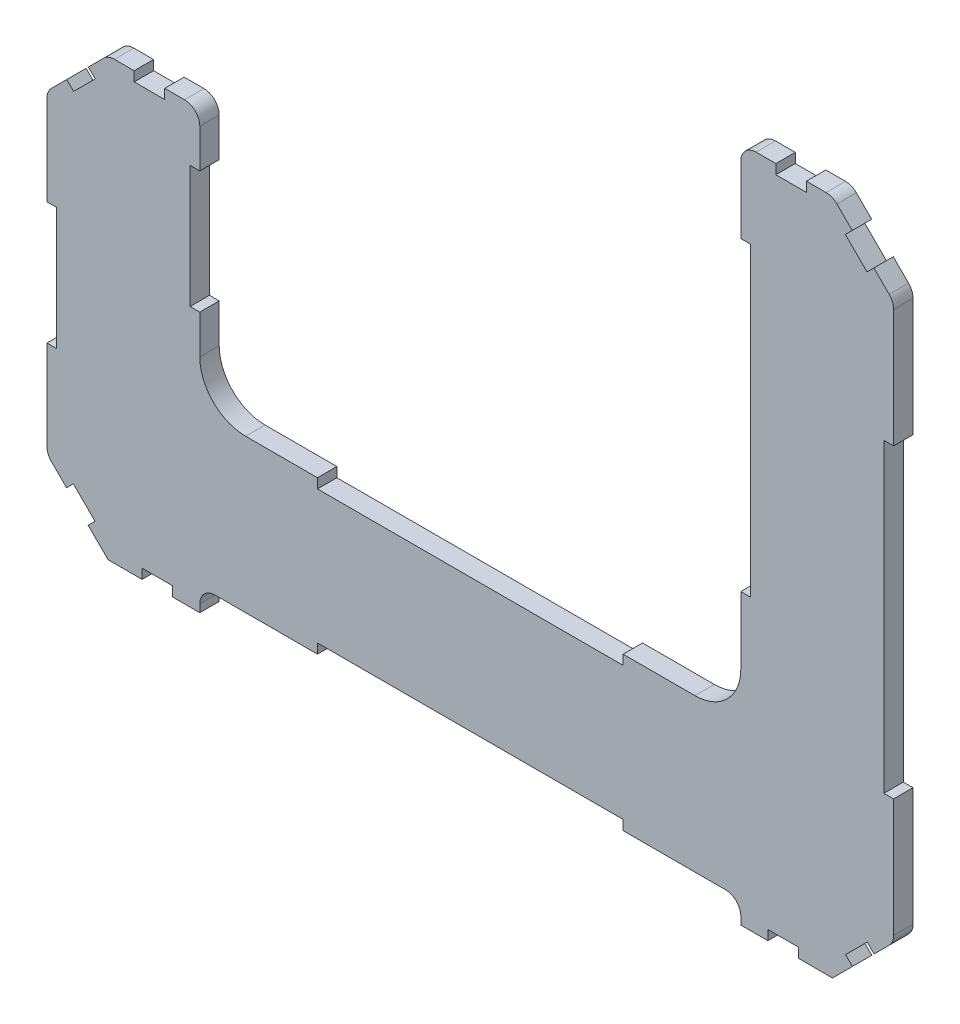
SolidWorks part; units mm, degrees
material "Cedar"
ref_plane "Front Plane" through (0, 0, 0) normal (0, 0, 1) x (1, 0, 0)
ref_plane "Top Plane" through (0, 0, 0) normal (0, 1, 0) x (1, 0, 0)
ref_plane "Right Plane" through (0, 0, 0) normal (1, 0, 0) x (0, 0, -1)
sketch "Sketch2" plane through (0, 0, 0) normal (0, 0, 1) x (1, 0, 0)
  line L0 (-138.5, 85.3385) -> (-88.5, 85.3385)
  line L1 (-88.5, 85.3385) -> (-88.5, 0)
  line L2 (-88.5, 0) -> (88.5, 0)
  line L3 (88.5, 0) -> (88.5, 164)
  line L4 (88.5, 164) -> (138.5, 164)
  line L5 (138.5, 164) -> (138.5, -57.5)
  line L6 (138.5, -57.5) -> (88.5, -57.5)
  line L7 (88.5, -57.5) -> (88.5, -50)
  line L8 (88.5, -50) -> (-88.5, -50)
  line L9 (-88.5, -50) -> (-88.5, -57.5)
  line L10 (-88.5, -57.5) -> (-138.5, -57.5)
  line L11 (-138.5, -57.5) -> (-138.5, 85.3385)
  line L12 (-33.5, 0) -> (-33.5, 124) construction
  point P10 (-33.5, 0)
  point P14 (88.5, 124)
  point P15 (-33.5, 85.3385)
  dimension "D1" = 124
  dimension "D2" = 122
  dimension "D3" = 55
  dimension "D4" = 40
  dimension "D5" = 50
  dimension "D6" = 50
  dimension "D7" = 7.5
extrude "Boss-Extrude1" add sketch "Sketch2" along normal blind 3.175 and the other way blind 3.175
chamfer "Chamfer1" distance 20 angle 45 4 edges at (-138.5, -57.5, 0) (138.5, -57.5, 0) (138.5, 164, 0) (-138.5, 85.3385, 0)
fillet "Fillet1" radius 15 2 edges at (88.5, 0, 0) (-88.5, 0, 0)
fillet "Fillet2" radius 5 10 edges at (138.5, -37.5, 0) (88.5, -50, 0) (-88.5, -50, 0) (-138.5, -37.5, 0) (-138.5, 65.3385, 0) (-118.5, 85.3385, 0) (-88.5, 85.3385, 0) (138.5, 144, 0) (118.5, 164, 0) (88.5, 164, 0)
sketch "Sketch3" plane through (0, 0, 3.175) normal (0, 0, 1) x (1, 0, 0)
  line L0 (-94.6381, 69.9757) -> (-94.6381, 14.7992)
  line L1 (-94.6381, 14.7992) -> (-97.8131, 14.7992)
  line L2 (-97.8131, 14.7992) -> (-97.8131, 69.9757)
  line L3 (-97.8131, 69.9757) -> (-94.6381, 69.9757)
  line L4 (-127.4635, 65.4691) -> (-114.3536, 78.579)
  line L5 (-114.3536, 78.579) -> (-112.1085, 76.3339)
  line L6 (-112.1085, 76.3339) -> (-125.2184, 63.2241)
  line L7 (-125.2184, 63.2241) -> (-127.4635, 65.4691)
  line L8 (-129.3392, 54.7846) -> (-126.1642, 54.7846)
  line L9 (-126.1642, 54.7846) -> (-126.1642, -28.3138)
  line L10 (-126.1642, -28.3138) -> (-129.3392, -28.3138)
  line L11 (-129.3392, -28.3138) -> (-129.3392, 54.7846)
  line L12 (-127.4635, -37.1329) -> (-125.2184, -34.8879)
  line L13 (-125.2184, -34.8879) -> (-110.9382, -49.1681)
  line L14 (-110.9382, -49.1681) -> (-113.1832, -51.4132)
  line L15 (-113.1832, -51.4132) -> (-127.4635, -37.1329)
  line L16 (-67.7784, -44.3183) -> (-67.7784, -41.1433)
  line L17 (-67.7784, -41.1433) -> (53.0181, -41.1433)
  line L18 (53.0181, -41.1433) -> (53.0181, -44.3183)
  line L19 (53.0181, -44.3183) -> (-67.7784, -44.3183)
  line L20 (114.9313, -49.5303) -> (117.1763, -51.7753)
  line L21 (117.1763, -51.7753) -> (131.7883, -37.1634)
  line L22 (131.7883, -37.1634) -> (129.5432, -34.9183)
  line L23 (129.5432, -34.9183) -> (114.9313, -49.5303)
  line L24 (-67.7784, -4.1746) -> (-67.7784, -7.3496)
  line L25 (-67.7784, -7.3496) -> (63.5847, -7.3496)
  line L26 (63.5847, -7.3496) -> (63.5847, -4.1746)
  line L27 (63.5847, -4.1746) -> (-67.7784, -4.1746)
  line L28 (92.7516, 20.9162) -> (91.2159, 151.9937)
  line L29 (91.2159, 151.9937) -> (94.3909, 151.9937)
  line L30 (94.3909, 151.9937) -> (95.9266, 20.9162)
  line L31 (95.9266, 20.9162) -> (92.7516, 20.9162)
  line L32 (96.8341, 161.8762) -> (96.8341, 158.7012)
  line L33 (96.8341, 158.7012) -> (112.5649, 158.7012)
  line L34 (112.5649, 158.7012) -> (112.5649, 161.8762)
  line L35 (112.5649, 161.8762) -> (96.8341, 161.8762)
  line L37 (117.7781, 156.4535) -> (120.0231, 158.6985)
  line L38 (120.0231, 158.6985) -> (133.8694, 144.8523)
  line L39 (133.8694, 144.8523) -> (131.6243, 142.6072)
  line L40 (131.6243, 142.6072) -> (117.7781, 156.4535)
  line L41 (129.9213, 134.1701) -> (133.0963, 134.1701)
  line L42 (133.0963, 134.1701) -> (133.0963, -24.961)
  line L43 (133.0963, -24.961) -> (129.9213, -24.961)
  line L44 (129.9213, -24.961) -> (129.9213, 134.1701)
  line L45 (118.5, -57.5) -> (137.0355, -38.9645) construction
  line L46 (-137.0355, -38.9645) -> (-118.5, -57.5) construction
  line L47 (-119.9645, 83.874) -> (-137.0355, 66.8029) construction
  line L48 (137.0355, 145.4645) -> (119.9645, 162.5355) construction
  dimension "D1" = 3.175
extrude "Cut-Extrude1" [suppressed] cut sketch "Sketch3" against normal through all
sketch "magnets" plane through (0, 0, 3.175) normal (0, 0, 1) x (1, 0, 0)
  point P0 (94.6751, 158.4052)
  point P1 (114.7572, -50)
  point P2 (131.9288, 140.6094)
  point P3 (131.9288, -32.8111)
  point P4 (0, -44.1618)
  point P5 (-114.0039, -50)
  point P6 (-130.8821, -32.8111)
  point P9 (-130.8821, 62.3605)
  point P10 (-93.5499, 79.7316)
  point P12 (0, -4.7392)
sketch "Sketch4" plane through (0, 0, 3.175) normal (0, 0, 1) x (1, 0, 0)
  line L0 (99.9645, 164) -> (99.9645, 160.825)
  line L1 (116.4289, 164) -> (93.5, 164) construction
  line L2 (99.9645, 160.825) -> (109.9645, 160.825)
  line L3 (109.9645, 160.825) -> (109.9645, 164)
  line L4 (124.9645, 157.5355) -> (122.7194, 155.2905)
  line L5 (137.0355, 145.4645) -> (119.9645, 162.5355) construction
  line L6 (122.7194, 155.2905) -> (129.7905, 148.2194)
  line L7 (129.7905, 148.2194) -> (132.0355, 150.4645)
  line L8 (88.5, 137) -> (91.675, 137)
  line L9 (88.5, 159) -> (88.5, 15) construction
  line L10 (91.675, 137) -> (91.675, 37)
  line L11 (91.675, 37) -> (88.5, 37)
  line L12 (138.5, 103.25) -> (135.325, 103.25)
  line L13 (138.5, -35.4289) -> (138.5, 141.9289) construction
  line L14 (135.325, 103.25) -> (135.325, 3.25)
  line L15 (135.325, 3.25) -> (138.5, 3.25)
  line L16 (-50, 0) -> (-50, -3.175)
  line L17 (73.5, 0) -> (-73.5, 0) construction
  line L18 (-50, -3.175) -> (50, -3.175)
  line L19 (50, -3.175) -> (50, 0)
  line L20 (-50, -50) -> (-50, -46.825)
  line L21 (-83.5, -50) -> (83.5, -50) construction
  line L22 (-50, -46.825) -> (50, -46.825)
  line L23 (50, -46.825) -> (50, -50)
  line L24 (-135.325, -6.0808) -> (-138.5, -6.0808)
  line L25 (-138.5, 63.2674) -> (-138.5, -35.4289) construction
  line L26 (-135.325, 33.9192) -> (-135.325, -6.0808)
  line L27 (-135.325, 33.9192) -> (-138.5, 33.9192)
  line L28 (-132.0355, 71.8029) -> (-129.7905, 69.5579)
  line L29 (-119.9645, 83.874) -> (-137.0355, 66.8029) construction
  line L30 (-129.7905, 69.5579) -> (-122.7194, 76.6289)
  line L31 (-122.7194, 76.6289) -> (-124.9645, 78.874)
  line L32 (-109.9645, 85.3385) -> (-109.9645, 82.1635)
  line L33 (-93.5, 85.3385) -> (-116.4289, 85.3385) construction
  line L35 (-109.9645, 82.1635) -> (-99.9645, 82.1635)
  line L36 (-88.5, 67.6692) -> (-91.675, 67.6692)
  line L37 (-88.5, 15) -> (-88.5, 80.3385) construction
  line L38 (-91.675, 67.6692) -> (-91.675, 27.6692)
  line L39 (-91.675, 27.6692) -> (-88.5, 27.6692)
  line L40 (-107.375, -57.5) -> (-107.375, -54.325)
  line L41 (-118.5, -57.5) -> (-88.5, -57.5) construction
  line L42 (-107.375, -54.325) -> (-97.375, -54.325)
  line L43 (-97.375, -54.325) -> (-97.375, -57.5)
  line L44 (97.375, -57.5) -> (97.375, -54.325)
  line L45 (88.5, -57.5) -> (118.5, -57.5) construction
  line L46 (97.375, -54.325) -> (107.375, -54.325)
  line L47 (107.375, -54.325) -> (107.375, -57.5)
  line L48 (-132.0988, -43.9012) -> (-129.8537, -41.6561)
  line L49 (-137.0355, -38.9645) -> (-118.5, -57.5) construction
  line L50 (-129.8537, -41.6561) -> (-122.7827, -48.7272)
  line L51 (-122.7827, -48.7272) -> (-125.0277, -50.9723)
  line L52 (125.0277, -50.9723) -> (122.7827, -48.7272)
  line L53 (118.5, -57.5) -> (137.0355, -38.9645) construction
  line L54 (122.7827, -48.7272) -> (129.8537, -41.6561)
  line L55 (129.8537, -41.6561) -> (132.0988, -43.9012)
  line L56 (-128.5633, -47.4367) -> (-126.3182, -45.1917) construction
  line L57 (-102.375, -57.5) -> (-102.375, -54.325)
  line L58 (102.375, -57.5) -> (102.375, -54.325)
  line L59 (-128.5, 75.3385) -> (-126.2549, 73.0934) construction
  line L60 (-104.9645, 82.1635) -> (-104.9645, 85.3385) construction
  line L61 (126.2549, 151.7549) -> (128.5, 154) construction
  line L62 (126.3182, -45.1917) -> (128.5633, -47.4367) construction
  line L63 (88.5, -57.5) -> (116.25, -57.5) construction
  line L64 (120.091, -55.909) -> (137.0355, -38.9645) construction
  line L65 (120.091, -55.909) -> (118.5, -57.5) construction
  line L66 (118.5, -57.5) -> (116.25, -57.5) construction
  line L67 (-88.5, -57.5) -> (-116.25, -57.5) construction
  line L68 (-116.25, -57.5) -> (-118.5, -57.5) construction
  line L69 (-118.5, -57.5) -> (-120.091, -55.909) construction
  line L70 (-120.091, -55.909) -> (-137.0355, -38.9645) construction
  line L71 (-99.9645, 82.1635) -> (-99.9645, 85.3385)
  point P95 (0, -46.825)
  point P97 (0, -50)
  point P99 (0, -3.175)
  point P101 (135.325, 53.25)
  point P103 (138.5, 53.25)
  point P104 (91.675, 87)
  point P105 (88.5, 87)
  point P106 (104.9645, 160.825)
  point P107 (104.9645, 164)
  point P108 (128.5, 154)
  point P109 (126.2549, 151.7549)
  point P112 (-135.325, 13.9192)
  point P113 (-138.5, 13.9192)
  point P114 (-91.675, 47.6692)
  point P115 (-88.5, 47.6692)
  point P116 (126.3182, -45.1917)
  point P117 (127.7678, -48.2322)
  line M1 (118.5, -57.5) -> (137.0355, -38.9645)
  line M3 (138.5, -35.4289) -> (138.5, 141.9289)
  line M5 (137.0355, 145.4645) -> (119.9645, 162.5355)
  line M7 (116.4289, 164) -> (93.5, 164)
  line M9 (88.5, 159) -> (88.5, 15)
  line M11 (73.5, 0) -> (-73.5, 0)
  line M13 (-88.5, 15) -> (-88.5, 80.3385)
  line M15 (-93.5, 85.3385) -> (-116.4289, 85.3385)
  line M17 (-119.9645, 83.874) -> (-137.0355, 66.8029)
  line M19 (-138.5, 63.2674) -> (-138.5, -35.4289)
  line M21 (-137.0355, -38.9645) -> (-118.5, -57.5)
  line M22 (-118.5, -57.5) -> (-88.5, -57.5)
  line M25 (-83.5, -50) -> (83.5, -50)
  line M28 (88.5, -57.5) -> (118.5, -57.5)
  dimension "D1" = 3.175
  dimension "D5" = 100
  dimension "D6" = 100
  dimension "D7" = 100
  dimension "D8" = 100
  dimension "D4" = 10
  dimension "D2" = 10
  dimension "D10" = 2.25
  dimension "D3" = 2.25
  dimension "D11" = 10
  dimension "D13" = 3.175
  dimension "D12" = 10
  dimension "D14" = 10
  dimension "D15" = 10
  dimension "D16" = 10
  dimension "D17" = 10
  dimension "D18" = 40
  dimension "D19" = 3.175
extrude "wall_slots" cut sketch "Sketch4" against normal blind 60 contours L26 L27 L24 M19 | L18 L19 L16 M11 | L23 L22 L20 M25 | L51 L50 L48 M21 | L57 L43 L42 M22 | L57 L42 L40 M22 | L38 L39 L36 M13 | L35 L71 L32 M15 | L30 L31 L28 M17 | L58 L47 L46 M28 | L58 L46 L44 M28 | L55 L54 L52 M1 | L14 L15 L12 M3 | L11 L10 L8 M9 | L2 L3 L0 M7 | L6 L7 L4 M5 region at (104.9645, 162.4125, 3.175) region at (127.3775, 152.8775, 3.175) region at (90.0875, 87, 3.175) region at (136.9125, 53.25, 3.175) region at (0, -1.5875, 3.175) region at (0, -48.4125, 3.175) region at (-136.9125, 13.9192, 3.175) region at (-127.3775, 74.2159, 3.175) region at (-104.9645, 83.751, 3.175) region at (-90.0875, 47.6692, 3.175) region at (-127.4407, -46.3142, 3.175) region at (-104.875, -55.9125, 3.175) region at (-99.875, -55.9125, 3.175) region at (127.4407, -46.3142, 3.175) region at (99.875, -55.9125, 3.175) region at (104.875, -55.9125, 3.175)
sketch "wall_measure" plane through (0, 0, 3.175) normal (0, 0, 1) x (1, 0, 0)
  line L0 (-116.4289, 85.3385) -> (-116.4289, 82.1635)
  line L1 (-116.4289, 82.1635) -> (-93.5, 82.1635)
  line L2 (-93.5, 82.1635) -> (-93.5, 85.3385)
  line L4 (93.5, 164) -> (93.5, 160.825)
  line L5 (93.5, 160.825) -> (116.4289, 160.825)
  line L6 (116.4289, 160.825) -> (116.4289, 164)
  line L7 (99.9645, 160.825) -> (109.9645, 160.825) construction
  line L8 (119.9645, 162.5355) -> (117.7194, 160.2905)
  line L9 (117.7194, 160.2905) -> (134.7905, 143.2194)
  line L10 (134.7905, 143.2194) -> (137.0355, 145.4645)
  line L11 (137.0355, 145.4645) -> (132.0355, 150.4645) construction
  line L12 (88.5, 159) -> (91.675, 159)
  line L13 (91.675, 159) -> (91.675, 15)
  line L14 (91.675, 15) -> (88.5, 15)
  line L15 (88.5, 37) -> (88.5, 15) construction
  line L16 (138.5, 141.9289) -> (135.325, 141.9289)
  line L17 (135.325, 141.9289) -> (135.325, -35.4289)
  line L18 (135.325, -35.4289) -> (138.5, -35.4289)
  line L19 (-73.5, 0) -> (-73.5, -3.175)
  line L20 (-73.5, -3.175) -> (73.5, -3.175)
  line L21 (73.5, -3.175) -> (73.5, 0)
  line L22 (-83.5, -50) -> (-83.5, -46.825)
  line L23 (-83.5, -46.825) -> (83.5, -46.825)
  line L24 (83.5, -46.825) -> (83.5, -50)
  line L25 (88.5, -55) -> (116.2868, -55)
  line L26 (116.2868, -55) -> (116.2868, -57.5)
  line L27 (137.0355, -38.9645) -> (134.7905, -36.7194)
  line L28 (134.7905, -36.7194) -> (117.8199, -53.69)
  line L29 (117.8199, -53.69) -> (120.065, -55.935)
  line L30 (118.5, -57.5) -> (125.0277, -50.9723) construction
  line L31 (122.7827, -48.7272) -> (129.8537, -41.6561) construction
  line L32 (116.2868, -57.5) -> (118.5, -57.5) construction
  line L33 (118.5, -57.5) -> (120.065, -55.935) construction
  line L34 (-138.5, 63.2674) -> (-133.5, 63.2674)
  line L35 (-133.5, 63.2674) -> (-133.5, -35.4289)
  line L36 (-133.5, -35.4289) -> (-138.5, -35.4289)
  line L37 (-88.5, 80.3385) -> (-91.675, 80.3385)
  line L38 (-91.675, 80.3385) -> (-91.675, 15)
  line L39 (-91.675, 15) -> (-88.5, 15)
  line L40 (-50, -46.825) -> (50, -46.825) construction
  line L41 (-50, -3.175) -> (50, -3.175) construction
  line L42 (135.325, 103.25) -> (135.325, 3.25) construction
  line L43 (91.675, 137) -> (91.675, 37) construction
  line L44 (122.7194, 155.2905) -> (129.7905, 148.2194) construction
  line L45 (-91.675, 67.6692) -> (-91.675, 27.6692) construction
  line L47 (-109.9645, 82.1635) -> (-99.9645, 82.1635) construction
  arc A0 (73.5, 0) -> (88.5, 15) centre (73.5, 15) ccw construction
  arc A1 (-88.5, 15) -> (-73.5, 0) centre (-73.5, 15) ccw construction
  dimension "D1" = 22.9289
  dimension "D2" = 22.9289
  dimension "D3" = 24.1421
  dimension "D4" = 144
  dimension "D5" = 177.3579
  dimension "D6" = 147
  dimension "D7" = 167
  dimension "D8" = 24
  dimension "D9" = 2.2132
  dimension "D10" = 27.7868
  dimension "D11" = 98.6963
  dimension "D12" = 65.3385
sketch "Sketch5" plane through (0, 0, 3.175) normal (0, 0, 1) x (1, 0, 0)
  line L72 (129.7905, 148.2194) -> (122.7194, 155.2905)
  line L73 (122.7194, 155.2905) -> (124.9645, 157.5355)
  line L74 (124.9645, 157.5355) -> (119.9645, 162.5355)
  line L75 (116.4289, 164) -> (109.9645, 164)
  line L76 (109.9645, 164) -> (109.9645, 160.825)
  line L77 (109.9645, 160.825) -> (99.9645, 160.825)
  line L78 (99.9645, 160.825) -> (99.9645, 164)
  line L79 (99.9645, 164) -> (93.5, 164)
  line L80 (88.5, 159) -> (88.5, 137)
  line L81 (88.5, 137) -> (91.675, 137)
  line L82 (91.675, 137) -> (91.675, 37)
  line L83 (91.675, 37) -> (88.5, 37)
  line L84 (88.5, 37) -> (88.5, 15)
  line L85 (73.5, 0) -> (50, 0)
  line L86 (50, 0) -> (50, -3.175)
  line L87 (50, -3.175) -> (-50, -3.175)
  line L88 (-50, -3.175) -> (-50, 0)
  line L89 (-50, 0) -> (-73.5, 0)
  line L90 (-88.5, 15) -> (-88.5, 27.6692)
  line L91 (-88.5, 27.6692) -> (-91.675, 27.6692)
  line L92 (-91.675, 27.6692) -> (-91.675, 67.6692)
  line L93 (-91.675, 67.6692) -> (-88.5, 67.6692)
  line L94 (-88.5, 67.6692) -> (-88.5, 80.3385)
  line L95 (-93.5, 85.3385) -> (-99.9645, 85.3385)
  line L96 (-99.9645, 85.3385) -> (-99.9645, 82.1635)
  line L97 (-99.9645, 82.1635) -> (-109.9645, 82.1635)
  line L98 (-109.9645, 82.1635) -> (-109.9645, 85.3385)
  line L99 (-109.9645, 85.3385) -> (-116.4289, 85.3385)
  line L100 (-119.9645, 83.874) -> (-124.9645, 78.874)
  line L101 (-124.9645, 78.874) -> (-122.7194, 76.6289)
  line L102 (-122.7194, 76.6289) -> (-129.7905, 69.5579)
  line L103 (-129.7905, 69.5579) -> (-132.0355, 71.8029)
  line L104 (-132.0355, 71.8029) -> (-137.0355, 66.8029)
  line L105 (-138.5, 63.2674) -> (-138.5, 33.9192)
  line L106 (-138.5, 33.9192) -> (-135.325, 33.9192)
  line L107 (-135.325, 33.9192) -> (-135.325, -6.0808)
  line L108 (-135.325, -6.0808) -> (-138.5, -6.0808)
  line L109 (-138.5, -6.0808) -> (-138.5, -35.4289)
  line L110 (-137.0355, -38.9645) -> (-132.0988, -43.9012)
  line L111 (-132.0988, -43.9012) -> (-129.8537, -41.6561)
  line L112 (-129.8537, -41.6561) -> (-122.7827, -48.7272)
  line L113 (-122.7827, -48.7272) -> (-125.0277, -50.9723)
  line L114 (-125.0277, -50.9723) -> (-118.5, -57.5)
  line L115 (-118.5, -57.5) -> (-107.375, -57.5)
  line L116 (-107.375, -57.5) -> (-107.375, -54.325)
  line L117 (-107.375, -54.325) -> (-97.375, -54.325)
  line L118 (-97.375, -54.325) -> (-97.375, -57.5)
  line L119 (-97.375, -57.5) -> (-88.5, -57.5)
  line L120 (-88.5, -57.5) -> (-88.5, -55)
  line L121 (-83.5, -50) -> (-50, -50)
  line L122 (-50, -50) -> (-50, -46.825)
  line L123 (-50, -46.825) -> (50, -46.825)
  line L124 (50, -46.825) -> (50, -50)
  line L125 (50, -50) -> (83.5, -50)
  line L126 (88.5, -55) -> (88.5, -57.5)
  line L127 (88.5, -57.5) -> (97.375, -57.5)
  line L128 (97.375, -57.5) -> (97.375, -54.325)
  line L129 (97.375, -54.325) -> (107.375, -54.325)
  line L130 (107.375, -54.325) -> (107.375, -57.5)
  line L131 (107.375, -57.5) -> (118.5, -57.5)
  line L132 (118.5, -57.5) -> (125.0277, -50.9723)
  line L133 (125.0277, -50.9723) -> (122.7827, -48.7272)
  line L134 (122.7827, -48.7272) -> (129.8537, -41.6561)
  line L135 (129.8537, -41.6561) -> (132.0988, -43.9012)
  line L136 (132.0988, -43.9012) -> (137.0355, -38.9645)
  line L137 (138.5, -35.4289) -> (138.5, 3.25)
  line L138 (138.5, 3.25) -> (135.325, 3.25)
  line L139 (135.325, 3.25) -> (135.325, 103.25)
  line L140 (135.325, 103.25) -> (138.5, 103.25)
  line L141 (138.5, 103.25) -> (138.5, 141.9289)
  line L142 (137.0355, 145.4645) -> (132.0355, 150.4645)
  line L143 (132.0355, 150.4645) -> (129.7905, 148.2194)
  line L144 (129.7905, 148.2194) -> (122.7194, 155.2905)
  line L145 (122.7194, 155.2905) -> (124.9645, 157.5355)
  line L146 (124.9645, 157.5355) -> (119.9645, 162.5355)
  line L147 (116.4289, 164) -> (109.9645, 164)
  line L148 (109.9645, 164) -> (109.9645, 160.825)
  line L149 (109.9645, 160.825) -> (99.9645, 160.825)
  line L150 (99.9645, 160.825) -> (99.9645, 164)
  line L151 (99.9645, 164) -> (93.5, 164)
  line L152 (88.5, 159) -> (88.5, 137)
  line L153 (88.5, 137) -> (91.675, 137)
  line L154 (91.675, 137) -> (91.675, 37)
  line L155 (91.675, 37) -> (88.5, 37)
  line L156 (88.5, 37) -> (88.5, 15)
  line L157 (73.5, 0) -> (50, 0)
  line L158 (50, 0) -> (50, -3.175)
  line L159 (50, -3.175) -> (-50, -3.175)
  line L160 (-50, -3.175) -> (-50, 0)
  line L161 (-50, 0) -> (-73.5, 0)
  line L162 (-88.5, 15) -> (-88.5, 27.6692)
  line L163 (-88.5, 27.6692) -> (-91.675, 27.6692)
  line L164 (-91.675, 27.6692) -> (-91.675, 67.6692)
  line L165 (-91.675, 67.6692) -> (-88.5, 67.6692)
  line L166 (-88.5, 67.6692) -> (-88.5, 80.3385)
  line L167 (-93.5, 85.3385) -> (-99.9645, 85.3385)
  line L168 (-99.9645, 85.3385) -> (-99.9645, 82.1635)
  line L169 (-99.9645, 82.1635) -> (-109.9645, 82.1635)
  line L170 (-109.9645, 82.1635) -> (-109.9645, 85.3385)
  line L171 (-109.9645, 85.3385) -> (-116.4289, 85.3385)
  line L172 (-119.9645, 83.874) -> (-124.9645, 78.874)
  line L173 (-124.9645, 78.874) -> (-122.7194, 76.6289)
  line L174 (-122.7194, 76.6289) -> (-129.7905, 69.5579)
  line L175 (-129.7905, 69.5579) -> (-132.0355, 71.8029)
  line L176 (-132.0355, 71.8029) -> (-137.0355, 66.8029)
  line L177 (-138.5, 63.2674) -> (-138.5, 33.9192)
  line L178 (-138.5, 33.9192) -> (-135.325, 33.9192)
  line L179 (-135.325, 33.9192) -> (-135.325, -6.0808)
  line L180 (-135.325, -6.0808) -> (-138.5, -6.0808)
  line L181 (-138.5, -6.0808) -> (-138.5, -35.4289)
  line L182 (-137.0355, -38.9645) -> (-132.0988, -43.9012)
  line L183 (-132.0988, -43.9012) -> (-129.8537, -41.6561)
  line L184 (-129.8537, -41.6561) -> (-122.7827, -48.7272)
  line L185 (-122.7827, -48.7272) -> (-125.0277, -50.9723)
  line L186 (-125.0277, -50.9723) -> (-118.5, -57.5)
  line L187 (-118.5, -57.5) -> (-107.375, -57.5)
  line L188 (-107.375, -57.5) -> (-107.375, -54.325)
  line L189 (-107.375, -54.325) -> (-97.375, -54.325)
  line L190 (-97.375, -54.325) -> (-97.375, -57.5)
  line L191 (-97.375, -57.5) -> (-88.5, -57.5)
  line L192 (-88.5, -57.5) -> (-88.5, -55)
  line L193 (-83.5, -50) -> (-50, -50)
  line L194 (-50, -50) -> (-50, -46.825)
  line L195 (-50, -46.825) -> (50, -46.825)
  line L196 (50, -46.825) -> (50, -50)
  line L197 (50, -50) -> (83.5, -50)
  line L198 (88.5, -55) -> (88.5, -57.5)
  line L199 (88.5, -57.5) -> (97.375, -57.5)
  line L200 (97.375, -57.5) -> (97.375, -54.325)
  line L201 (97.375, -54.325) -> (107.375, -54.325)
  line L202 (107.375, -54.325) -> (107.375, -57.5)
  line L203 (107.375, -57.5) -> (118.5, -57.5)
  line L204 (118.5, -57.5) -> (125.0277, -50.9723)
  line L205 (125.0277, -50.9723) -> (122.7827, -48.7272)
  line L206 (122.7827, -48.7272) -> (129.8537, -41.6561)
  line L207 (129.8537, -41.6561) -> (132.0988, -43.9012)
  line L208 (132.0988, -43.9012) -> (137.0355, -38.9645)
  line L209 (138.5, -35.4289) -> (138.5, 3.25)
  line L210 (138.5, 3.25) -> (135.325, 3.25)
  line L211 (135.325, 3.25) -> (135.325, 103.25)
  line L212 (135.325, 103.25) -> (138.5, 103.25)
  line L213 (138.5, 103.25) -> (138.5, 141.9289)
  line L214 (137.0355, 145.4645) -> (132.0355, 150.4645)
  line L215 (132.0355, 150.4645) -> (129.7905, 148.2194)
  arc A12 (119.9645, 162.5355) -> (116.4289, 164) centre (116.4289, 159) ccw
  arc A13 (93.5, 164) -> (88.5, 159) centre (93.5, 159) ccw
  arc A14 (73.5, 0) -> (88.5, 15) centre (73.5, 15) ccw
  arc A15 (-88.5, 15) -> (-73.5, 0) centre (-73.5, 15) ccw
  arc A16 (-88.5, 80.3385) -> (-93.5, 85.3385) centre (-93.5, 80.3385) ccw
  arc A17 (-116.4289, 85.3385) -> (-119.9645, 83.874) centre (-116.4289, 80.3385) ccw
  arc A18 (-137.0355, 66.8029) -> (-138.5, 63.2674) centre (-133.5, 63.2674) ccw
  arc A19 (-138.5, -35.4289) -> (-137.0355, -38.9645) centre (-133.5, -35.4289) ccw
  arc A20 (-83.5, -50) -> (-88.5, -55) centre (-83.5, -55) ccw
  arc A21 (88.5, -55) -> (83.5, -50) centre (83.5, -55) ccw
  arc A22 (137.0355, -38.9645) -> (138.5, -35.4289) centre (133.5, -35.4289) ccw
  arc A23 (138.5, 141.9289) -> (137.0355, 145.4645) centre (133.5, 141.9289) ccw
  arc A24 (119.9645, 162.5355) -> (116.4289, 164) centre (116.4289, 159) ccw
  arc A25 (93.5, 164) -> (88.5, 159) centre (93.5, 159) ccw
  arc A26 (73.5, 0) -> (88.5, 15) centre (73.5, 15) ccw
  arc A27 (-88.5, 15) -> (-73.5, 0) centre (-73.5, 15) ccw
  arc A28 (-88.5, 80.3385) -> (-93.5, 85.3385) centre (-93.5, 80.3385) ccw
  arc A29 (-116.4289, 85.3385) -> (-119.9645, 83.874) centre (-116.4289, 80.3385) ccw
  arc A30 (-137.0355, 66.8029) -> (-138.5, 63.2674) centre (-133.5, 63.2674) ccw
  arc A31 (-138.5, -35.4289) -> (-137.0355, -38.9645) centre (-133.5, -35.4289) ccw
  arc A32 (-83.5, -50) -> (-88.5, -55) centre (-83.5, -55) ccw
  arc A33 (88.5, -55) -> (83.5, -50) centre (83.5, -55) ccw
  arc A34 (137.0355, -38.9645) -> (138.5, -35.4289) centre (133.5, -35.4289) ccw
  arc A35 (138.5, 141.9289) -> (137.0355, 145.4645) centre (133.5, 141.9289) ccw
  dimension "D1" = 0
equation "\"dX\"= 122mm"
equation "\"dY\"= 124mm"
equation "\"hmotor\"= 50mm"
equation "\"D1@Sketch2\"=\"dY\""
equation "\"D2@Sketch2\"=\"dX\""
equation "\"D5@Sketch2\"=\"hmotor\""
equation "\"D6@Sketch2\"=\"hmotor\""
equation "\"t_wood\"= 0.25in"
equation "\"D1@Boss-Extrude1\"=\"t_wood\"/2"
equation "\"D2@Boss-Extrude1\"=\"t_wood\"/2"
equation "\"D1@Sketch3\"=\"t_wood\"/2"
equation "\"D1@Sketch4\"=\"t_wood\"/2"
equation "\"D13@Sketch4\"=\"t_wood\"/2"
equation "\"D19@Sketch4\"=\"t_wood\"/2"
